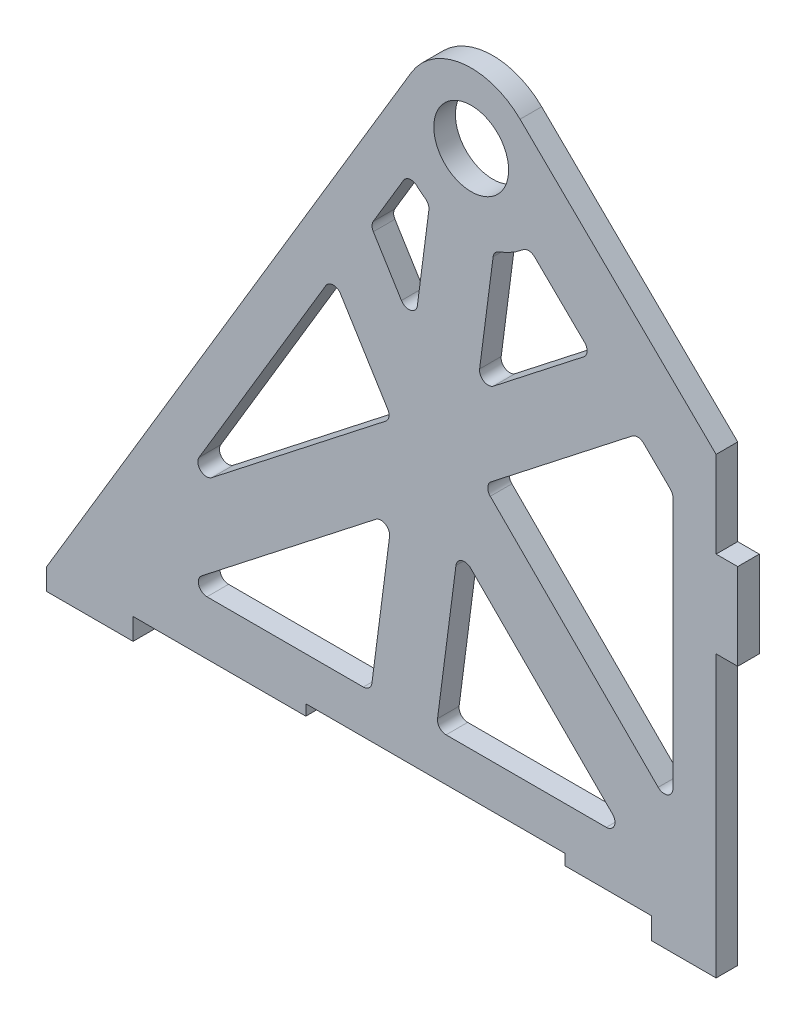
SolidWorks part; units mm, degrees
ref_plane "Front Plane" through (0, 0, 0) normal (0, 0, 1) x (1, 0, 0)
ref_plane "Top Plane" through (0, 0, 0) normal (0, 1, 0) x (1, 0, 0)
ref_plane "Right Plane" through (0, 0, 0) normal (1, 0, 0) x (0, 0, -1)
sketch "Sketch2" plane through (0, 0, 0) normal (0, 0, 1) x (1, 0, 0)
  line L0 (0, 2.5421) -> (203.2, 2.5421) construction
  line L1 (25.4, 2.5421) -> (76.2, 2.5421)
  line L2 (0, 2.5421) -> (107.2144, 181.9515)
  line L4 (76.2, 2.5421) -> (76.2, 5.7171)
  line L6 (0, 2.5421) -> (0, -3.8079)
  line L7 (0, -3.8079) -> (25.4, -3.8079)
  line L8 (25.4, 2.5421) -> (25.4, -3.8079)
  line L13 (76.2, 5.7171) -> (152.4, 5.7171)
  line L14 (152.4, 5.7171) -> (152.4, 2.5421)
  line L16 (152.4, 2.5421) -> (177.8, 2.5421)
  line L17 (0, -33.6061) -> (203.2, -33.6061) construction
  line L18 (177.8, 2.5421) -> (177.8, -3.8079)
  line L19 (177.8, -3.8079) -> (196.85, -3.8079)
  line L20 (196.85, -3.8079) -> (196.85, 78.7421)
  line L22 (196.85, 129.5421) -> (139.2046, 186.0765)
  line L23 (196.85, 104.1421) -> (196.85, 129.5421)
  line L24 (196.85, 104.1421) -> (203.2, 104.1421)
  line L26 (196.85, 78.7421) -> (203.2, 78.7421)
  line L27 (203.2, 104.1421) -> (203.2, 78.7421)
  arc A0 (139.2046, 186.0765) -> (107.2144, 181.9515) centre (124.8331, 171.4226) ccw
  circle A1 centre (124.8331, 171.4226) radius 11 construction
  circle A2 centre (124.8331, 171.4226) radius 4 construction
  circle A3 centre (124.8331, 171.4226) radius 11
  dimension "D3" = 22
  dimension "D4" = 9.525
  dimension "D5" = 8
  dimension "D6" = 22
  dimension "D1" = 168.8805
  dimension "D2" = 124.8331
  dimension "D7" = 6.35
  dimension "D8" = 25.4
  dimension "D9" = 19.05
  dimension "D10" = 6.35
  dimension "D11" = 44.45
  dimension "D12" = 203.2
  dimension "D13" = 76.2
  dimension "D14" = 3.175
  dimension "D15" = 133.35
  dimension "D16" = 6.35
  dimension "D17" = 25.4
  dimension "D18" = 25.4
extrude "Boss-Extrude1" add sketch "Sketch2" along normal blind 6.35
sketch "Sketch4" plane through (0, 0, 6.35) normal (0, 0, 1) x (1, 0, 0)
  line L0 (106.6403, 156.2334) -> (10.9017, -3.9728)
  line L1 (124.8331, 171.4226) -> (184.15, 113.2489)
  line L2 (118.1161, 175.4367) -> (10.9017, -3.9728) construction
  line L3 (24.2818, 18.4171) -> (184.15, 18.4171)
  line L4 (124.8331, 171.4226) -> (103.2992, 5.7171) construction
  line L5 (134.2787, 170.1951) -> (112.7448, 4.4896)
  line L6 (115.3875, 172.6501) -> (93.8537, 6.9445)
  line L7 (24.2818, 18.4171) -> (114.0662, 88.5698) construction
  line L8 (18.4173, 25.9226) -> (108.2017, 96.0754)
  line L9 (30.1462, 10.9115) -> (119.9306, 81.0643)
  line L10 (114.0662, 88.5698) -> (89.7368, 127.9475) construction
  line L11 (105.9631, 83.5633) -> (81.6336, 122.9409)
  line L12 (122.1693, 93.5763) -> (97.8399, 132.954)
  line L13 (0, 2.5421) -> (0, -3.8079)
  line L14 (0, -3.8079) -> (25.4, -3.8079)
  line L15 (25.4, -3.8079) -> (25.4, 2.5421)
  line L16 (25.4, 2.5421) -> (76.2, 2.5421)
  line L17 (76.2, 2.5421) -> (76.2, 5.7171)
  line L18 (76.2, 5.7171) -> (152.4, 5.7171)
  line L19 (152.4, 5.7171) -> (152.4, 2.5421)
  line L20 (152.4, 2.5421) -> (177.8, 2.5421)
  line L21 (177.8, -3.8079) -> (196.85, -3.8079)
  line L22 (177.8, 2.5421) -> (177.8, -3.8079)
  line L23 (152.4, 2.5421) -> (177.8, 2.5421)
  line L24 (196.85, -3.8079) -> (196.85, 78.7421)
  line L25 (107.2144, 181.9515) -> (0, 2.5421)
  line L26 (0, 2.5421) -> (0, -3.8079)
  line L27 (0, -3.8079) -> (25.4, -3.8079)
  line L28 (25.4, -3.8079) -> (25.4, 2.5421)
  line L29 (25.4, 2.5421) -> (76.2, 2.5421)
  line L30 (76.2, 2.5421) -> (76.2, 5.7171)
  line L31 (76.2, 5.7171) -> (152.4, 5.7171)
  line L32 (152.4, 5.7171) -> (152.4, 2.5421)
  line L34 (177.8, -3.8079) -> (196.85, -3.8079)
  line L35 (177.8, 2.5421) -> (177.8, -3.8079)
  line L38 (107.2144, 181.9515) -> (0, 2.5421)
  line L39 (114.0662, 88.5698) -> (172.0162, 133.8489) construction
  line L40 (108.2017, 96.0754) -> (166.1517, 141.3545)
  line L41 (119.9306, 81.0643) -> (177.8807, 126.3433)
  line L42 (114.0662, 88.5698) -> (184.15, 18.4171) construction
  line L43 (120.8047, 95.3017) -> (190.8885, 25.1489)
  line L44 (107.3277, 81.838) -> (177.4115, 11.6852)
  line L45 (97.8399, 132.954) -> (84.7663, 154.1138)
  line L46 (166.1517, 141.3545) -> (164.1076, 139.7573)
  line L47 (184.15, 113.2489) -> (184.15, 18.4171)
  line L60 (196.85, -3.8079) -> (196.85, 78.7421)
  line L61 (196.85, 129.5421) -> (139.2046, 186.0765)
  line L62 (196.85, 129.5421) -> (139.2046, 186.0765)
  line L68 (196.85, 78.7421) -> (203.2, 78.7421)
  line L69 (196.85, 78.7421) -> (203.2, 78.7421)
  line L70 (203.2, 78.7421) -> (203.2, 104.1421)
  line L71 (203.2, 78.7421) -> (203.2, 104.1421)
  line L72 (203.2, 104.1421) -> (196.85, 104.1421)
  line L73 (203.2, 104.1421) -> (196.85, 104.1421)
  line L74 (196.85, 104.1421) -> (196.85, 129.5421)
  line L75 (196.85, 104.1421) -> (196.85, 129.5421)
  arc A0 (134.2787, 170.1951) -> (115.3875, 172.6501) centre (124.8331, 171.4226) ccw
  arc A1 (139.2046, 186.0765) -> (107.2144, 181.9515) centre (124.8331, 171.4226) ccw
  arc A2 (139.2046, 186.0765) -> (107.2144, 181.9515) centre (124.8331, 171.4226) ccw
  arc A3 (93.8537, 6.9445) -> (112.7448, 4.4896) centre (103.2992, 5.7171) ccw
  circle A4 centre (124.8331, 171.4226) radius 23.7
  circle A5 centre (124.8331, 171.4226) radius 23.7
  arc A6 (18.4173, 25.9226) -> (30.1462, 10.9115) centre (24.2818, 18.4171) ccw
  arc A7 (119.9306, 81.0643) -> (108.2017, 96.0754) centre (114.0662, 88.5698) ccw
  arc A8 (105.9631, 83.5633) -> (122.1693, 93.5763) centre (114.0662, 88.5698) ccw
  arc A9 (97.8399, 132.954) -> (81.6336, 122.9409) centre (89.7368, 127.9475) ccw
  arc A10 (108.2017, 96.0754) -> (119.9306, 81.0643) centre (114.0662, 88.5698) ccw
  arc A11 (177.8807, 126.3433) -> (166.1517, 141.3545) centre (172.0162, 133.8489) ccw
  arc A12 (120.8047, 95.3017) -> (107.3277, 81.838) centre (114.0662, 88.5698) ccw
  arc A13 (177.4115, 11.6852) -> (190.8885, 25.1489) centre (184.15, 18.4171) ccw
  point P18 (114.0662, 88.5698)
  point P31 (69.174, 53.4934)
  point P39 (101.9015, 108.2586)
  point P44 (143.0412, 111.2094)
  point P51 (149.1081, 53.4934)
  dimension "D6" = 9.525
  dimension "D4" = 12.7
  dimension "D5" = 12.7
  dimension "D1" = 0
  dimension "D2" = 12.7
  dimension "D3" = 12.7
extrude "Cut-Extrude1" cut sketch "Sketch4" against normal through all contours A5 L0 L45 L12 L6 | A5 L5 L40 L46 | L41 L43 | L44 L5 L3 | L9 L3 L6 | L8 L11 L0 region at (105.1664, 138.0225, 6.35) region at (140.4766, 134.8244, 6.35) region at (74.5143, 83.5502, 6.35) region at (165.0491, 82.2709, 6.35) region at (78.908, 34.5324, 6.35) region at (135.4189, 34.9901, 6.35)
fillet "Fillet1" radius 2.54 21 edges at (101.6272, 66.7629, 3.175) (95.3445, 18.4171, 3.175) (39.7522, 18.4171, 3.175) (128.4096, 87.6893, 3.175) (112.5909, 151.1293, 3.175) (108.076, 116.3867, 3.175) (106.6403, 156.2334, 3.175) (84.2318, 118.7357, 3.175) (101.4783, 90.8221, 3.175) (37.8327, 41.0928, 3.175) (131.482, 148.6744, 3.175) (170.6862, 18.4171, 3.175) (114.5547, 18.4171, 3.175) (121.0159, 68.1363, 3.175) (95.2417, 137.1592, 3.175) (141.7538, 154.828, 3.175) (160.2189, 136.7188, 3.175) (126.5051, 110.3767, 3.175) (184.15, 31.8941, 3.175) (173.9388, 123.2633, 3.175) (184.15, 113.2489, 3.175)
